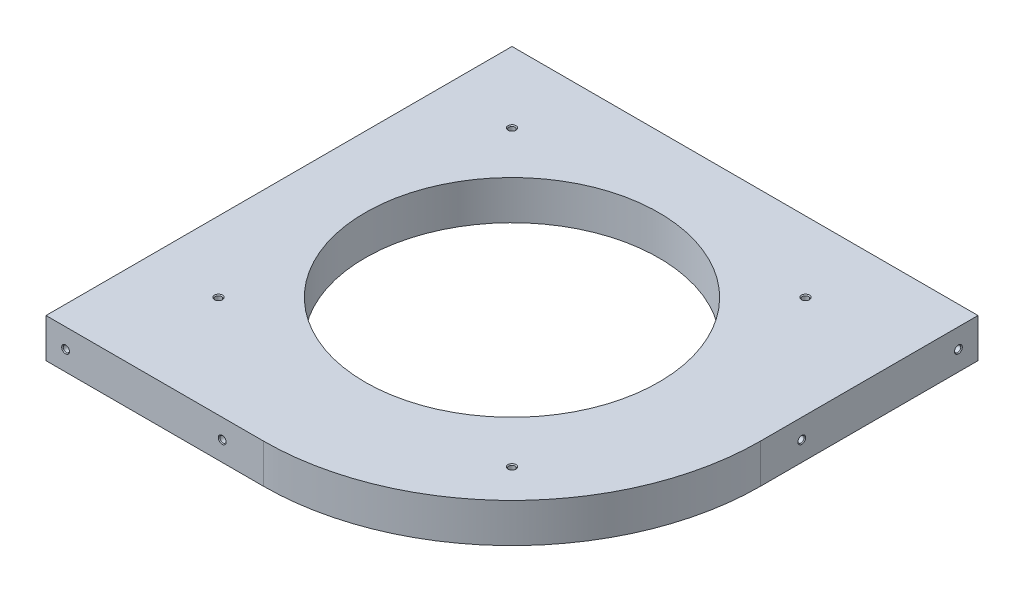
SolidWorks part; units mm, degrees
other "Markup1"
sketch "Sketch10" plane through (101, 10, 101) normal (0.4075, 0.0648, 0.9109) x (0.9078, -0.1373, -0.3964)
ref_plane "Front Plane" through (0, 0, 0) normal (0, 0, 1) x (1, 0, 0)
ref_plane "Top Plane" through (0, 0, 0) normal (0, 1, 0) x (1, 0, 0)
ref_plane "Right Plane" through (0, 0, 0) normal (1, 0, 0) x (0, 0, -1)
sketch "Sketch1" plane through (0, 0, 0) normal (0, 1, 0) x (1, 0, 0)
  line L1 (-55.5, 55.5) -> (63.5, 55.5)
  line L2 (-55.5, 55.5) -> (-55.5, -63.5)
  line L4 (88.5, 55.5) -> (88.5, 0) construction
  line L5 (63.5, 0) -> (88.5, 0) construction
  line L6 (-53, 0) -> (-55.5, 0) construction
  line L7 (0, 53) -> (0, 55.5) construction
  line L8 (0, -37.5) -> (0, -63.5) construction
  line L9 (0, -63.5) -> (-55.5, -63.5)
  line L10 (0, -63.5) -> (0, -88.5) construction
  line L11 (-55.5, -63.5) -> (-55.5, -88.5) construction
  line L12 (-55.5, -88.5) -> (0, -88.5) construction
  line L13 (63.5, 0) -> (63.5, 55.5)
  line L14 (63.5, 55.5) -> (88.5, 55.5) construction
  circle A0 centre (0, 0) radius 37.5
  circle A1 centre (0, 0) radius 53 construction
  arc A3 (0, -63.5) -> (63.5, 0) centre (0, 0) ccw
  point P18 (37.4767, -37.4767)
  point P22 (-37.4767, -37.4767)
  point P23 (-37.4767, 37.4767)
  point P24 (37.4767, 37.4767)
  point P25 (0, 0)
  point P28 (0, 0)
  dimension "D1" = 75
  dimension "D2" = 106
  dimension "D5" = 2.5
  dimension "D6" = 25
  dimension "D3" = 4
  dimension "D7" = 26
extrude "Boss-Extrude1" add sketch "Sketch1" along normal blind 10
hole_wizard "M2x0.4 Tapped Hole2" positions "Sketch4" profile "Sketch3" tap size "M2x0.4" standard "ANSI Metric" end condition through all
sketch "Sketch4" plane through (0, 10, 0) normal (0, 1, 0) x (1, 0, 0)
  point P31 (37.4767, 37.4767)
  point P33 (-37.4767, 37.4767)
  point P35 (-37.4767, -37.4767)
  point P37 (37.4767, -37.4767)
sketch "Sketch3" plane through (37.4767, 10, -37.4767) normal (1, 0, 0) x (0, 0, 1)
  line L0 (0, 0) -> (0, 10)
  line L1 (0, 10) -> (0.8, 10)
  line L2 (0.8, 10) -> (0.8, 0.225)
  line L3 (0.8, 0.225) -> (1.025, 0)
  line L5 (1.025, 0) -> (0, 0)
  line L6 (-0.8, 0.225) -> (-1.025, 0) construction
  line L11 (0, -6.35) -> (0, 107.95) construction
  dimension "Thru Tap Drill Dia." = 1.6
  dimension "Thru Tap Drill Depth" = 10
  dimension "Near C'Sink Dia." = 2.05
  dimension "Near C'Sink Angle" = 90
hole_wizard "M2x0.4 Tapped Hole1" positions "3DSketch1" profile "Sketch5" tap size "M2x0.4" standard "ANSI Metric"
sketch3d "3DSketch1"
  line L0 (-55.5, 10, 63.5) -> (-55.5, 0, 63.5) construction
  line L1 (-55.5, 10, 63.5) -> (0, 10, 63.5) construction
  line L2 (-50.5, 5, 63.5) -> (-10.5, 5, 63.5) construction
  line L4 (63.5, 10, 0) -> (63.5, 10, -55.5) construction
  line L5 (63.5, 10, -55.5) -> (63.5, 0, -55.5) construction
  line L6 (63.5, 5, -50.5) -> (63.5, 5, -10.5) construction
  point P0 (63.5, 5, -50.5)
  point P2 (63.5, 5, -10.5)
  point P4 (-50.5, 5, 63.5)
  point P6 (-10.5, 5, 63.5)
  dimension "D1" = 5
  dimension "D2" = 5
  dimension "D3" = 45
  dimension "D4" = 5
  dimension "D5" = 5
  dimension "D6" = 45
sketch "Sketch5" plane through (63.5, 5, -50.5) normal (0, 1, 0) x (0, 0, -1)
  line L0 (0, 0) -> (0, 6.4807)
  line L1 (0, 6.4807) -> (0.8, 6)
  line L2 (0.8, 6) -> (0.8, 0)
  line L5 (0.8, 0) -> (0, 0)
  line L10 (0, 6.4807) -> (-0.8, 6) construction
  line L11 (0, -6.35) -> (0, 107.95) construction
  dimension "Tap Drill Dia." = 1.6
  dimension "Tap Drill Depth" = 6
  dimension "Drill Angle" = 118
cosmetic thread "Hole Thread5" parameters "D1"=4, "D2"=2
cosmetic thread "Hole Thread6" parameters "D1"=4, "D2"=2
cosmetic thread "Hole Thread7" parameters "D1"=4, "D2"=2
cosmetic thread "Hole Thread8" parameters "D1"=4, "D2"=2
chamfer "Chamfer1" distance 0.2 angle 45 4 edges at (63.5, 5, -51.3) (63.5, 5, -11.3) (-49.7, 5, 63.5) (-9.7, 5, 63.5)
